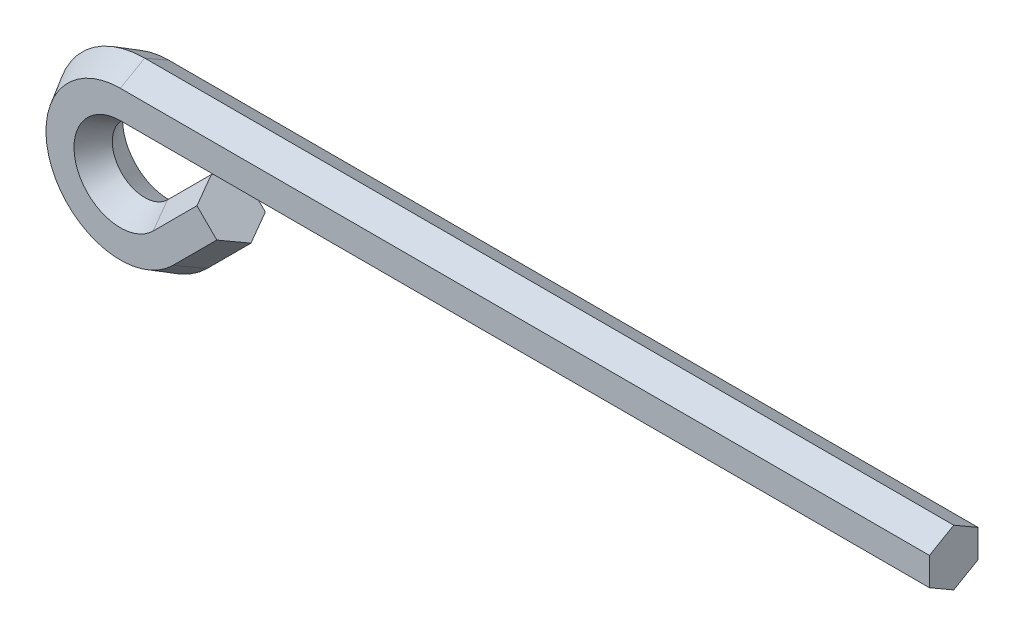
SolidWorks part; units mm, degrees
material "PW20:29:Sc:0:"
ref_plane "Front" through (0, 0, 0) normal (0, 0, 1) x (1, 0, 0)
ref_plane "Top" through (0, 0, 0) normal (0, 1, 0) x (1, 0, 0)
ref_plane "Right" through (0, 0, 0) normal (1, 0, 0) x (0, 0, -1)
sketch "Sketch1" plane through (0, 0, 0) normal (0, 0, 1) x (1, 0, 0)
  line L0 (100, 4) -> (0, 4)
  line L1 (2.8284, -2.8284) -> (8.2426, 2.5858)
  line L2 (8.2426, 2.5858) -> (9.6569, 4) construction
  arc A0 (0, 4) -> (2.8284, -2.8284) centre (0, 0) ccw
  dimension "Center_Rad" = 4
  dimension "Length" = 100
  dimension "Overlap" = 2
  dimension "Angle" = 45
ref_plane "Plane4" through (100, 4, 0) normal (-1, 0, 0) x (0, 0, 1)
sketch "Sketch2" plane through (100, 4, 0) normal (-1, 0, 0) x (0, 0, 1)
  line L0 (0, 0) -> (0, 6.9282) construction
  line L1 (-3, 5.1962) -> (0, 6.9282)
  line L2 (-3, 1.7321) -> (-3, 5.1962)
  line L3 (0, 0) -> (3, 1.7321)
  line L4 (3, 1.7321) -> (3, 5.1962)
  line L5 (3, 5.1962) -> (0, 6.9282)
  line L6 (0, 0) -> (-3, 1.7321)
  line L7 (3, 1.7321) -> (-3, 5.1962) construction
  line L8 (3, 5.1962) -> (-3, 1.7321) construction
  dimension "Hex_Diam" = 6
sweep "Base-Sweep" add profiles "Sketch2" path "Sketch1"
ref_axis "center_axis" [suppressed] through (0, 0, 53) along (0, 0, -1)
